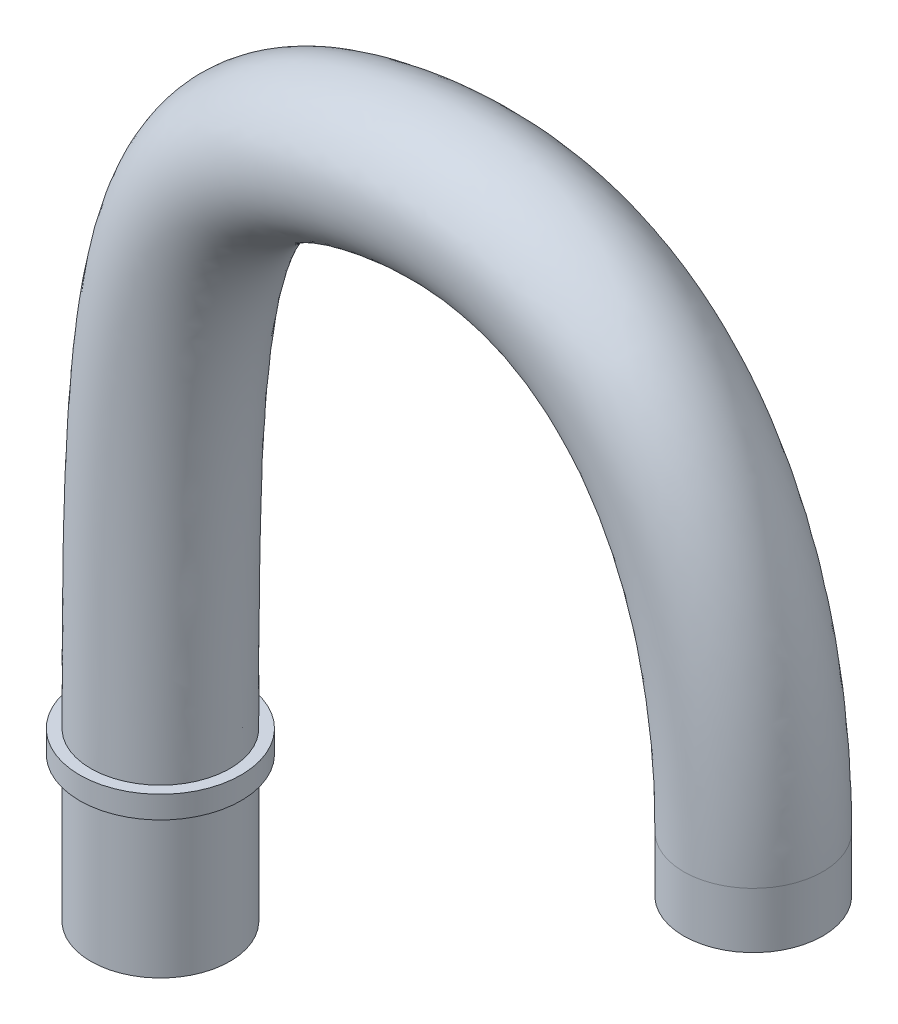
SolidWorks part; units mm, degrees
ref_plane "Płaszczyzna przednia" through (0, 0, 0) normal (0, 0, 1) x (1, 0, 0)
ref_plane "Płaszczyzna górna" through (0, 0, 0) normal (0, 1, 0) x (1, 0, 0)
ref_plane "Płaszczyzna prawa" through (0, 0, 0) normal (1, 0, 0) x (0, 0, -1)
sketch "Sketch1" plane through (0, 0, 0) normal (0, 0, 1) x (1, 0, 0)
  line L1 (25.5636, 41.2004) -> (0.3636, 41.2004) construction
  spline S0 degree 3 poles (-93.5364, 0) (-93.5364, 68.8979) (-92.6957, 106.938) (-8.9755, 119.82) (12.9636, 82.9446) (12.9636, 41.2004) knots 0 0 0 0 0.466992 0.566992 1 1 1 1
  point P0 (-48.8889, 113.3493)
  point P4 (-93.5248, 1.4733)
sketch "Sketch2" plane through (0, 0, 0) normal (0, 1, 0) x (1, 0, 0)
  circle A0 centre (-93.5364, 0) radius 12.5
  circle A2 centre (-93.5364, 0) radius 10.5
  dimension "D2" = 25
  dimension "D1" = 2
sweep "Sweep1" add profiles "Sketch2" path "Sketch1"
extrude "Boss-Extrude1" add sketch "Sketch2<2>" against normal blind 26 contours A0 | A2
sketch "Sketch2<2>" plane through (0, 0, 0) normal (0, 1, 0) x (1, 0, 0) same geometry as "Sketch2"
sketch "Sketch5" plane through (0, 0, 0) normal (0, 1, 0) x (1, 0, 0)
  circle A0 centre (-93.5364, 0) radius 14.5
  circle A1 centre (-93.5364, 0) radius 12.5 construction
  circle A2 centre (-93.5364, 0) radius 11.5969
  dimension "D1" = 2
extrude "Boss-Extrude5" add sketch "Sketch5" along normal blind 4
sketch "Sketch6" plane through (0, 41.2004, 0) normal (0, -1, 0) x (1, 0, 0)
  circle A0 centre (12.9636, 0) radius 12.5
  circle A1 centre (12.9636, 0) radius 10.5
  dimension "D1" = 2
extrude "Boss-Extrude6" add sketch "Sketch6" along normal blind 10
